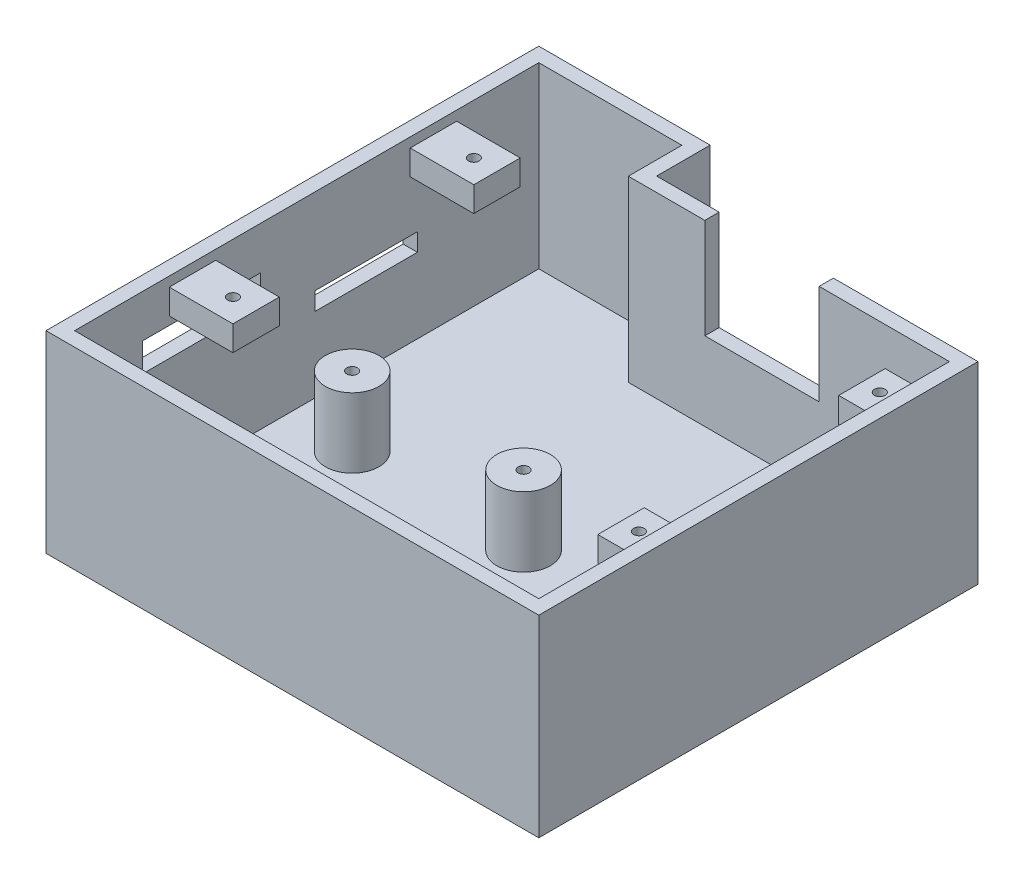
SolidWorks part; units mm, degrees
ref_plane "Front Plane" through (0, 0, 0) normal (0, 0, 1) x (1, 0, 0)
ref_plane "Top Plane" through (0, 0, 0) normal (0, 1, 0) x (1, 0, 0)
ref_plane "Right Plane" through (0, 0, 0) normal (1, 0, 0) x (0, 0, -1)
sketch "Sketch1" plane through (0, 0, 0) normal (0, 1, 0) x (1, 0, 0)
  line L0 (-65, 57.5) -> (-65, 72.5)
  line L1 (-65, -57.5) -> (65, -57.5)
  line L2 (-65, -57.5) -> (-65, 57.5)
  line L3 (-65, 57.5) -> (65, 57.5)
  line L4 (65, -57.5) -> (65, 57.5)
  line L5 (-65, -57.5) -> (65, 57.5) construction
  line L6 (-65, 57.5) -> (65, -57.5) construction
  line L7 (-69, -61.5) -> (69, -61.5)
  line L8 (-69, -61.5) -> (-69, 61.5)
  line L9 (-69, 61.5) -> (-65, 61.5) construction
  line L10 (69, -61.5) -> (69, 61.5)
  line L11 (-69, -61.5) -> (69, 61.5) construction
  line L12 (-69, 61.5) -> (69, -61.5) construction
  line L13 (-65, 72.5) -> (-24.9293, 72.5)
  line L14 (-24.9293, 72.5) -> (-24.9293, 57.5)
  line L15 (-24.9293, 61.5) -> (-21, 61.5) construction
  line L18 (-21, 76.5) -> (-69, 76.5)
  line L19 (-69, 76.5) -> (-69, 61.5)
  line L20 (-21, 61.5) -> (69, 61.5)
  line L21 (-65, 61.5) -> (-24.9293, 61.5) construction
  line L22 (-21, 61.5) -> (-21, 76.5)
  line L23 (-21, 57.5) -> (-21, 61.5) construction
  point P0 (0, 0)
  point P6 (0, 0)
  dimension "D1" = 130
  dimension "D2" = 115
  dimension "D3" = 4
  dimension "D4" = 4
  dimension "D5" = 4
  dimension "D6" = 15
  dimension "D7" = 48
extrude "Boss-Extrude1" add sketch "Sketch1" along normal blind 4 contours L7 L10 L20 L22 L18 L19 L8
extrude "Boss-Extrude2" add sketch "Sketch1<5>" along normal blind 50 from surface contours L20 L22 L18 L19 L8 L7 L10 L13 L14 L3 L4 L1 L2 L0 region at (-67.0484, 0, 0) starting at face at (-7, 4, -25.5)
sketch "Sketch1<5>" plane through (0, 0, 0) normal (0, 1, 0) x (1, 0, 0) same geometry as "Sketch1"
sketch "Sketch3" plane through (0, 4, 0) normal (0, 1, 0) x (1, 0, 0)
  line L0 (-46.8629, 2.1037) -> (1.1371, 2.1037) construction
  line L1 (65, 57.5) -> (-24.9293, 57.5) construction
  line L2 (-65, 72.5) -> (-65, -57.5) construction
  circle A0 centre (-46.8629, 2.1037) radius 1.5
  circle A1 centre (1.1371, 2.1037) radius 1.5
  circle A2 centre (-46.8629, 2.1037) radius 7.5
  circle A3 centre (1.1371, 2.1037) radius 7.5
  dimension "D2" = 3
  dimension "D3" = 15
  dimension "D5" = 18.1371
  dimension "D1" = 48
  dimension "D4" = 55.3963
extrude "Boss-Extrude3" add sketch "Sketch3" along normal blind 19.5
sketch "Sketch4" plane through (-65, 0, 0) normal (1, 0, 0) x (0, 0, -1)
  line L0 (72.5, 54) -> (-57.5, 54) construction
  line L1 (-30.97, 51.3) -> (-17.97, 51.3)
  line L2 (-30.97, 51.3) -> (-30.97, 44.3)
  line L3 (-30.97, 44.3) -> (-17.97, 44.3)
  line L4 (-17.97, 51.3) -> (-17.97, 44.3)
  line L5 (-30.97, 51.3) -> (-17.97, 44.3) construction
  line L6 (-30.97, 44.3) -> (-17.97, 51.3) construction
  line L7 (36.5, 51.3) -> (49.5, 51.3)
  line L8 (36.5, 51.3) -> (36.5, 44.3)
  line L9 (36.5, 44.3) -> (49.5, 44.3)
  line L10 (49.5, 51.3) -> (49.5, 44.3)
  line L11 (36.5, 51.3) -> (49.5, 44.3) construction
  line L12 (36.5, 44.3) -> (49.5, 51.3) construction
  point P0 (-24.47, 47.8)
  point P5 (43, 47.8)
  dimension "D1" = 13
  dimension "D2" = 13
  dimension "D3" = 7
  dimension "D4" = 7
  dimension "D5" = 2.7
  dimension "D6" = 67.47
  dimension "D7" = 8
extrude "Boss-Extrude4" add sketch "Sketch4" along normal blind 17.81
sketch "Sketch5" plane through (65, 0, 0) normal (-1, 0, 0) x (0, 0, 1)
  line L0 (30.97, 44.3) -> (17.97, 44.3) construction
  line L1 (30.97, 51.3) -> (30.97, 44.3) construction
  line L2 (30.97, 51.3) -> (17.97, 51.3) construction
  line L3 (17.97, 51.3) -> (17.97, 44.3) construction
  line L4 (-36.5, 51.3) -> (-49.5, 51.3) construction
  line L5 (-49.5, 51.3) -> (-49.5, 44.3) construction
  line L6 (-36.5, 44.3) -> (-49.5, 44.3) construction
  line L7 (-36.5, 51.3) -> (-36.5, 44.3) construction
  line L8 (30.97, 44.3) -> (17.97, 44.3)
  line L9 (30.97, 51.3) -> (30.97, 44.3)
  line L10 (30.97, 51.3) -> (17.97, 51.3)
  line L11 (17.97, 51.3) -> (17.97, 44.3)
  line L12 (-36.5, 51.3) -> (-49.5, 51.3)
  line L13 (-49.5, 51.3) -> (-49.5, 44.3)
  line L14 (-36.5, 44.3) -> (-49.5, 44.3)
  line L15 (-36.5, 51.3) -> (-36.5, 44.3)
extrude "Boss-Extrude5" add sketch "Sketch5" along normal blind 10
sketch "Sketch6" plane through (0, 51.3, 0) normal (0, 1, 0) x (1, 0, 0)
  line L0 (-47.19, -17.97) -> (-65, -30.97) construction
  line L3 (-65, 36.5) -> (-47.19, 49.5) construction
  line L4 (55, -17.97) -> (65, -30.97) construction
  line L5 (55, -30.97) -> (55, -17.97) construction
  line L6 (-47.19, -30.97) -> (-65, -30.97) construction
  line L7 (-65, 72.5) -> (-65, -57.5) construction
  line L8 (55, 36.5) -> (65, 49.5) construction
  circle A0 centre (-53.69, 43) radius 1.5
  circle A1 centre (-53.69, -24.47) radius 1.5
  circle A2 centre (60, -24.47) radius 1.5
  circle A3 centre (60, 43) radius 1.5
  point P16 (60, -24.47)
  point P19 (60, 43)
  dimension "D1" = 3
  dimension "D2" = 113.69
extrude "Cut-Extrude1" cut sketch "Sketch6" against normal up to next
sketch "Sketch7" plane through (0, 0, -57.5) normal (0, 0, 1) x (1, 0, 0)
  line L0 (65, 54) -> (-24.9293, 54) construction
  line L1 (-3.5, 26) -> (28.5, 26)
  line L2 (-3.5, 26) -> (-3.5, 54)
  line L3 (-3.5, 54) -> (28.5, 54)
  line L4 (28.5, 26) -> (28.5, 54)
  line L5 (12.5, 26) -> (12.5, 54) construction
  line L6 (65, 54) -> (65, 4) construction
  dimension "D1" = 32
  dimension "D2" = 28
  dimension "D3" = 36.5
extrude "Cut-Extrude2" cut sketch "Sketch7" against normal up to next
sketch "Sketch8" plane through (-65, 0, 0) normal (1, 0, 0) x (0, 0, -1)
  line L0 (-57.5, 54) -> (-57.5, 4) construction
  line L1 (-38.5, 42) -> (-5.5, 42)
  line L2 (-38.5, 42) -> (-38.5, 34)
  line L3 (-38.5, 34) -> (-5.5, 34)
  line L4 (-5.5, 42) -> (-5.5, 34)
  line L5 (9.8174, 30) -> (38.5174, 30)
  line L6 (9.8174, 30) -> (9.8174, 25)
  line L7 (9.8174, 25) -> (38.5174, 25)
  line L8 (38.5174, 30) -> (38.5174, 25)
  line L9 (72.5, 54) -> (-57.5, 54) construction
  dimension "D1" = 28.7
  dimension "D2" = 33
  dimension "D3" = 19
  dimension "D4" = 8
  dimension "D5" = 5
  dimension "D6" = 24
  dimension "D7" = 12
extrude "Cut-Extrude3" cut sketch "Sketch8" against normal up to next
